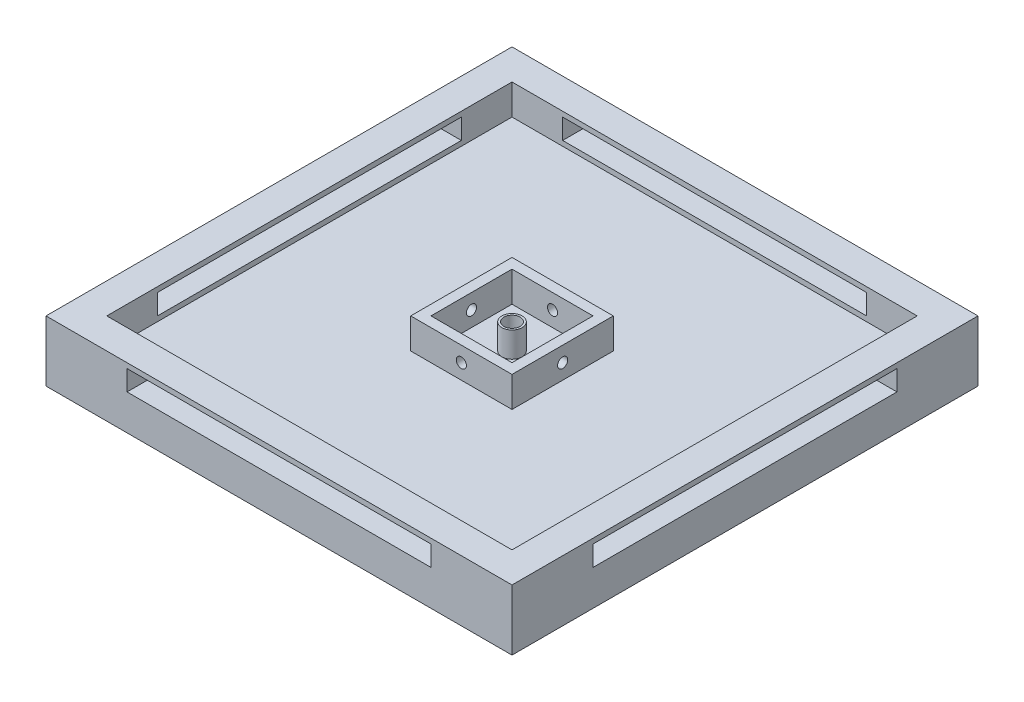
SolidWorks part; units mm, degrees
ref_plane "Front Plane" through (0, 0, 0) normal (0, 0, 1) x (1, 0, 0)
ref_plane "Top Plane" through (0, 0, 0) normal (0, 1, 0) x (1, 0, 0)
ref_plane "Right Plane" through (0, 0, 0) normal (1, 0, 0) x (0, 0, -1)
sketch "Sketch1" plane through (0, 0, 0) normal (0, 1, 0) x (1, 0, 0)
  line L1 (0, 0) -> (-40, 0)
  line L2 (0, 0) -> (0, -40)
  line L3 (0, -40) -> (-40, -40)
  line L4 (-40, 0) -> (-40, -40)
  dimension "D1" = 40
  dimension "D2" = 40
extrude "Boss-Extrude1" add sketch "Sketch1" along normal blind 3
sketch "Sketch2" plane through (0, 0, 0) normal (1, 0, 0) x (0, 0, -1)
  line L1 (0, 0) -> (-40, 0)
  line L2 (0, 0) -> (0, 6)
  line L3 (0, 6) -> (-40, 6)
  line L4 (-40, 0) -> (-40, 6)
  dimension "D1" = 6
extrude "Boss-Extrude2" add sketch "Sketch2" along normal blind 3 separate body
sketch "Sketch4" plane through (0, 0, 40) normal (0, 0, 1) x (1, 0, 0)
  line L1 (3, 0) -> (-40, 0)
  line L2 (3, 0) -> (3, 6)
  line L3 (3, 6) -> (-40, 6)
  line L4 (-40, 0) -> (-40, 6)
extrude "Boss-Extrude3" add sketch "Sketch4" along normal blind 3
sketch "Sketch5" plane through (0, 0, 0) normal (0, 0, -1) x (-1, 0, 0)
  line L1 (-3, 0) -> (40, 0)
  line L2 (-3, 0) -> (-3, 6)
  line L3 (-3, 6) -> (40, 6)
  line L4 (40, 0) -> (40, 6)
extrude "Boss-Extrude4" add sketch "Sketch5" along normal blind 3
sketch "Sketch6" plane through (-40, 0, 0) normal (-1, 0, 0) x (0, 0, 1)
  line L1 (-3, 0) -> (43, 0)
  line L2 (-3, 0) -> (-3, 6)
  line L3 (-3, 6) -> (43, 6)
  line L4 (43, 0) -> (43, 6)
extrude "Boss-Extrude5" add sketch "Sketch6" along normal blind 3
sketch "Sketch7" plane through (0, 0, 0) normal (-1, 0, 0) x (0, 0, 1)
  line L0 (0, 6) -> (40, 6) construction
  line L1 (0, 3) -> (0, 6) construction
  line L3 (35, 5.5) -> (5, 5.5)
  line L4 (35, 5.5) -> (35, 3.5)
  line L5 (35, 3.5) -> (5, 3.5)
  line L6 (5, 5.5) -> (5, 3.5)
  line L7 (35, 5.5) -> (5, 3.5) construction
  line L8 (35, 3.5) -> (5, 5.5) construction
  point P0 (20, 6)
  point P1 (0, 4.5)
  point P4 (20, 4.5)
  point P7 (20, 4.5)
  dimension "D1" = 2
  dimension "D2" = 30
extrude "Cut-Extrude1" cut sketch "Sketch7" against normal blind 3
ref_plane "Plane1" through (0, 0, 0) normal (0.7071, 0, 0.7071) x (0.7071, 0, -0.7071)
mirror "Mirror1" about plane through (0, 0, 0) normal (0.7071, 0, 0.7071) of "Cut-Extrude1"
ref_plane "Plane2" through (-20, 0, 20) normal (0.7071, 0, -0.7071) x (-0.7071, 0, -0.7071)
mirror "Mirror2" about plane through (-20, 0, 20) normal (0.7071, 0, -0.7071) of "Mirror1"
sketch "Sketch8" plane through (0, 3, 0) normal (0, 1, 0) x (1, 0, 0)
  line L0 (0, -40) -> (0, 0) construction
  line L1 (0, 0) -> (-40, 0) construction
  line L3 (-15, -25) -> (-25, -25)
  line L4 (-15, -25) -> (-15, -15)
  line L5 (-15, -15) -> (-25, -15)
  line L6 (-25, -25) -> (-25, -15)
  line L7 (-15, -25) -> (-25, -15) construction
  line L8 (-15, -15) -> (-25, -25) construction
  line L9 (-16.0002, -23.9998) -> (-23.9998, -23.9998)
  line L10 (-16.0002, -23.9998) -> (-16.0002, -16.0002)
  line L11 (-16.0002, -16.0002) -> (-23.9998, -16.0002)
  line L12 (-23.9998, -23.9998) -> (-23.9998, -16.0002)
  line L13 (-16.0002, -23.9998) -> (-23.9998, -16.0002) construction
  line L14 (-16.0002, -16.0002) -> (-23.9998, -23.9998) construction
  point P0 (0, -20)
  point P1 (-20, 0)
  point P4 (-20, -20)
  point P7 (-20, -20)
  point P12 (-20, -20)
  dimension "D1" = 10
  dimension "D2" = 10
extrude "Boss-Extrude6" add sketch "Sketch8" along normal blind 3
sketch "Sketch9" plane through (0, 3, 0) normal (0, 1, 0) x (1, 0, 0)
  circle A0 centre (-20, -20) radius 1
extrude "Cut-Extrude2" cut sketch "Sketch9" against normal blind 3
sketch "Sketch10" plane through (-25, 0, 0) normal (-1, 0, 0) x (0, 0, 1)
  line L0 (15, 3) -> (25, 3) construction
  line L1 (15, 6) -> (15, 3) construction
  circle A0 centre (20, 4.5) radius 0.5
  point P0 (20, 3)
  point P1 (15, 4.5)
  point P4 (20, 4.5)
extrude "Cut-Extrude3" cut sketch "Sketch10" against normal blind 10
mirror "Mirror3" about plane through (-20, 0, 20) normal (0.7071, 0, -0.7071) of "Cut-Extrude3"
sketch "Sketch11" plane through (0, 3, 0) normal (0, 1, 0) x (1, 0, 0)
  circle A0 centre (-20, -20) radius 1
  circle A1 centre (-20, -20) radius 0.8
extrude "Boss-Extrude7" add sketch "Sketch11" along normal blind 2.5 and the other way blind 5
sketch "Sketch12" plane through (-23.9998, 0, 0) normal (1, 0, 0) x (0, 0, -1)
  circle A0 centre (-20, 4.5) radius 0.125
  dimension "D1" = 0.25
